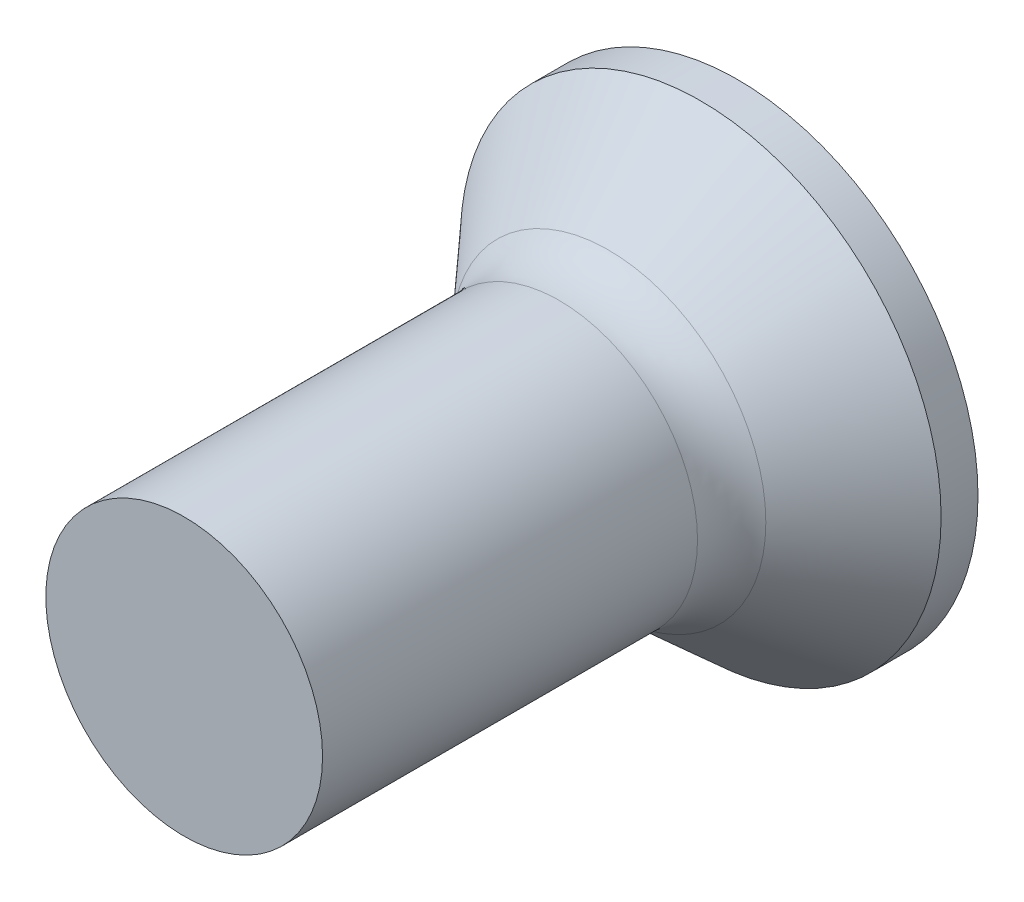
SolidWorks part; units mm, degrees
ref_plane "Спереди" through (0, 0, 0) normal (0, 0, 1) x (1, 0, 0)
ref_plane "Сверху" through (0, 0, 0) normal (0, 1, 0) x (1, 0, 0)
ref_plane "Справа" through (0, 0, 0) normal (1, 0, 0) x (0, 0, -1)
sketch "Эскиз1" plane through (0, 0, 0) normal (1, 0, 0) x (0, 0, -1)
  line L0 (-3, 0) -> (3, 0)
  line L1 (3, 0) -> (3, 2.6054)
  line L2 (3, 2.6054) -> (2.6, 2.6054)
  line L3 (2.6, 2.6054) -> (1.6, 1.7054)
  line L4 (1.0648, 1.5) -> (-3, 1.5)
  line L5 (-3, 1.5) -> (-3, 0)
  line L6 (3, 0) -> (3.2916, 0) construction
  arc A0 (1.0648, 1.5) -> (1.6, 1.7054) centre (1.0648, 2.3) ccw
  dimension "D3" = 0.8
  dimension "D1" = 3
  dimension "D2" = 6
  dimension "D4" = 0.9
  dimension "D5" = 0.4
  dimension "D6" = 1
revolve "Повернуть1" add sketch "Эскиз1" angle 360 about L6
sketch "Эскиз2" plane through (0, 0, 0) normal (1, 0, 0) x (0, 0, -1)
  line L0 (0, 0) -> (3, 0) construction
  line L1 (3, 0) -> (3, 1.4972)
  line L2 (3, 1.4972) -> (1, 0.5)
  line L3 (1, 0.5) -> (1, 0)
  line L4 (1, 0) -> (3, 0)
  line L5 (3, -2.6054) -> (3, 2.6054) construction
  dimension "D1" = 0.5
  dimension "D2" = 26.5
  dimension "D3" = 2
extrude "Вырез-Вытянуть1" cut sketch "Эскиз2" against normal blind 0.35 and the other way blind 0.35
pattern_circular "Круговой массив1" count 4 over 360 about axis through (0, 0, -3) along (0, 0, 1) of "Вырез-Вытянуть1"
sketch "Эскиз3" plane through (0, 0, 0) normal (1, 0, 0) x (0, 0, -1)
  line L0 (0, 0) -> (3.5491, 0) construction
  line L1 (0.8, 0) -> (0.9787, 0.55)
  line L2 (0.9787, 0.55) -> (3, 0.55)
  line L3 (3, 0.55) -> (3, 0)
  line L4 (3, 0) -> (0.8, 0)
  line L5 (3, -2.6054) -> (3, 2.6054) construction
  dimension "D1" = 72
  dimension "D2" = 2.2
  dimension "D3" = 1.1
revolve "Вырез-Повернуть1" cut sketch "Эскиз3" angle 360 about L0
scale "Масштаб1" scale about centroid uniform scaling yes scale factor 0.5
